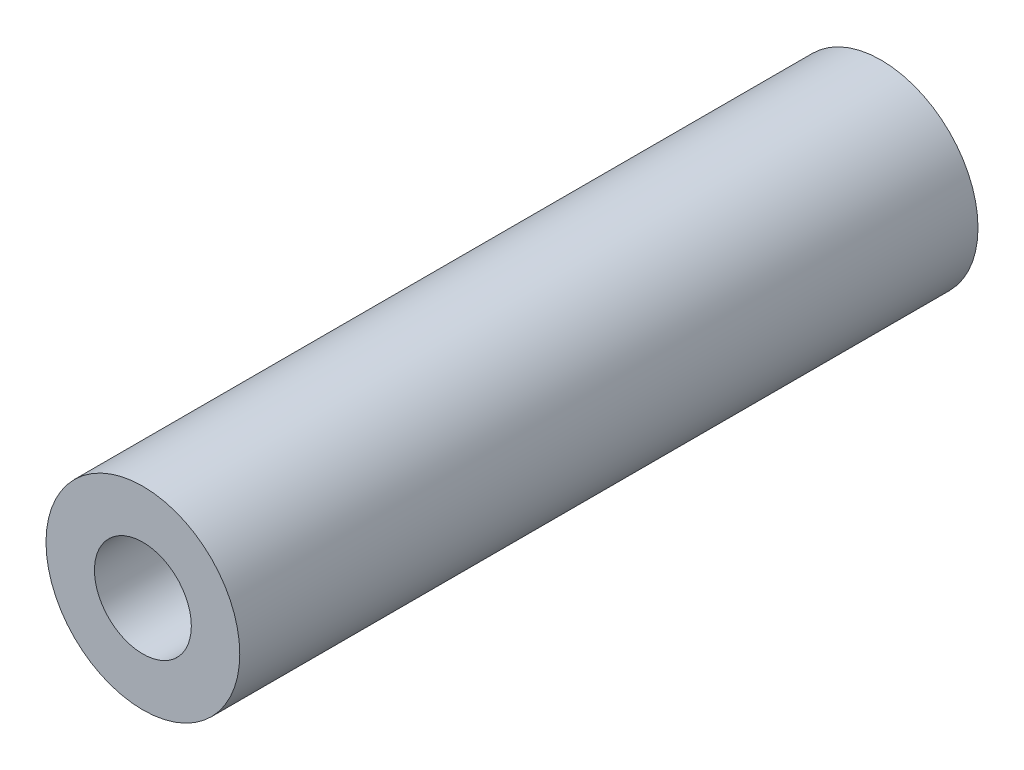
SolidWorks part; units mm, degrees
ref_plane "Front Plane" through (0, 0, 0) normal (0, 0, 1) x (1, 0, 0)
ref_plane "Top Plane" through (0, 0, 0) normal (0, 1, 0) x (1, 0, 0)
ref_plane "Right Plane" through (0, 0, 0) normal (1, 0, 0) x (0, 0, -1)
sketch "Sketch2" plane through (0, 0, 0) normal (0, 0, 1) x (1, 0, 0)
  line L0 (-19.7949, 2.8571) -> (-9.8974, 71.4286)
  line L1 (9.8974, 71.4286) -> (19.7949, 2.8571)
  line L2 (-2.5, 9.6825) -> (-2.5, 12)
  line L3 (-2.5, 12) -> (2.5, 12)
  line L4 (2.5, 12) -> (2.5, 9.6825)
  arc A0 (-19.7949, 2.8571) -> (19.7949, 2.8571) centre (0, 0) ccw
  arc A1 (-2.5, 9.6825) -> (2.5, 9.6825) centre (0, 0) ccw
  arc A2 (9.8974, 71.4286) -> (-9.8974, 71.4286) centre (0, 70) ccw
  circle A3 centre (0, 70) radius 5
  point P12 (0, 12)
  dimension "D1" = 20
  dimension "D2" = 40
  dimension "D3" = 10
  dimension "D4" = 20
  dimension "D5" = 70
  dimension "D6" = 12
  dimension "D7" = 5
extrude "Boss-Extrude1" add sketch "Sketch2" along normal blind 10
sketch "Sketch3" plane through (0, 0, 10) normal (0, 0, 1) x (1, 0, 0)
  circle A0 centre (0, 70) radius 10
  arc A1 (9.8974, 71.4286) -> (-9.8974, 71.4286) centre (0, 70) ccw construction
  circle A2 centre (0, 70) radius 5
  circle A3 centre (0, 70) radius 5 construction
extrude "Boss-Extrude2" add sketch "Sketch3" along normal blind 76.2
extrude "Boss-Extrude3" add sketch "Sketch2<2>" along normal blind 22 from surface starting at face at (10, 70, 86.2)
sketch "Sketch2<2>" plane through (0, 0, 0) normal (0, 0, 1) x (1, 0, 0) same geometry as "Sketch2"
sketch "Sketch5" plane through (0, 0, 108.2) normal (0, 0, 1) x (1, 0, 0)
  circle A0 centre (0, 0) radius 65
  dimension "D1" = 130
extrude "Boss-Extrude4" add sketch "Sketch5" against normal up to surface (22 mm away) up to face at (0, 5.9206, 86.2)
sketch "Sketch6" plane through (0, 0, 108.2) normal (0, 0, 1) x (1, 0, 0)
  circle A0 centre (0, 0) radius 55
  dimension "D1" = 110
extrude "Cut-Extrude1" cut sketch "Sketch6" against normal up to surface (22 mm away) contours A0 up to face at (0, 32.6245, 86.2)
sketch "Sketch7" plane through (0, 0, 108.2) normal (0, 0, 1) x (1, 0, 0)
  circle A0 centre (0, 0) radius 80
  arc A1 (9.8974, 71.4286) -> (-9.8974, 71.4286) centre (0, 70) ccw construction
extrude "Cut-Extrude2" cut sketch "Sketch7" against normal up to surface (22 mm away) up to face at (55, 0, 86.2)
sketch "Sketch8" plane through (0, 0, 0) normal (0, 0, -1) x (-1, 0, 0)
  circle A0 centre (0, 0) radius 80
  arc A1 (9.8974, 71.4286) -> (-9.8974, 71.4286) centre (0, 70) ccw construction
extrude "Cut-Extrude3" cut sketch "Sketch8" against normal up to surface (10 mm away) up to face at (0, 28.5714, 10)
